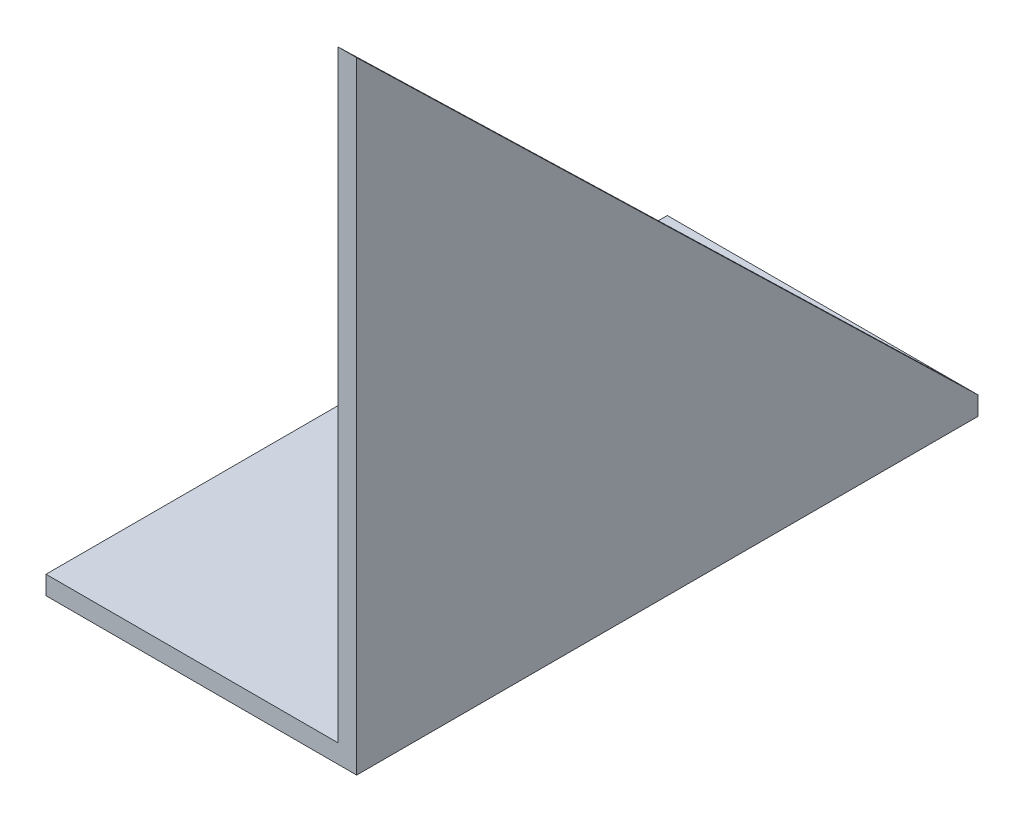
SolidWorks part; units mm, degrees
material "Acero al carbono no aleado"
ref_plane "Alzado" through (0, 0, 0) normal (0, 0, 1) x (1, 0, 0)
ref_plane "Planta" through (0, 0, 0) normal (0, 1, 0) x (1, 0, 0)
ref_plane "Vista lateral" through (0, 0, 0) normal (1, 0, 0) x (0, 0, -1)
sketch "Croquis1" plane through (0, 0, 0) normal (0, 0, 1) x (1, 0, 0)
  line L1 (1.5, -50) -> (-1.5, -50)
  line L2 (1.5, -50) -> (1.5, 50)
  line L3 (1.5, 50) -> (-1.5, 50)
  line L4 (-1.5, -50) -> (-1.5, 50)
  line L5 (1.5, -50) -> (-1.5, 50) construction
  line L6 (1.5, 50) -> (-1.5, -50) construction
  line L7 (-1.5, -50) -> (-48.5, -50)
  line L8 (-1.5, -50) -> (-1.5, -47)
  line L9 (-1.5, -47) -> (-48.5, -47)
  line L10 (-48.5, -50) -> (-48.5, -47)
  point P0 (0, 0)
  dimension "D1" = 3
  dimension "D2" = 3
  dimension "D3" = 50
  dimension "D4" = 100
extrude "Saliente-Extruir1" add sketch "Croquis1" along normal mid plane 100 contours L4 L1 L2 L3 | L7 L10 L9 L8 region at (0, 0, 0)
sketch "Croquis3" plane through (-1.5, 0, 0) normal (-1, 0, 0) x (0, 0, 1)
  line L0 (50, 50) -> (-50, -47)
  line L4 (-50, -47) -> (50, -47)
  line L5 (50, -47) -> (50, 50)
  line L6 (50, 50) -> (-50, 50)
  line L7 (-50, 50) -> (-50, -47)
  line L8 (-50, -47) -> (50, -47)
  line L9 (50, -47) -> (50, 50)
  line L10 (50, 50) -> (-50, 50)
  line L11 (-50, 50) -> (-50, -47)
  line M7 (50, 50) -> (-50, 50)
  line M8 (-50, 50) -> (-50, -47)
  dimension "D1" = 0
extrude "Cortar-Extruir2" cut sketch "Croquis3" against normal blind 100 contours L0 M7 M8 region at (-1.5, 17.6667, -16.6667)
